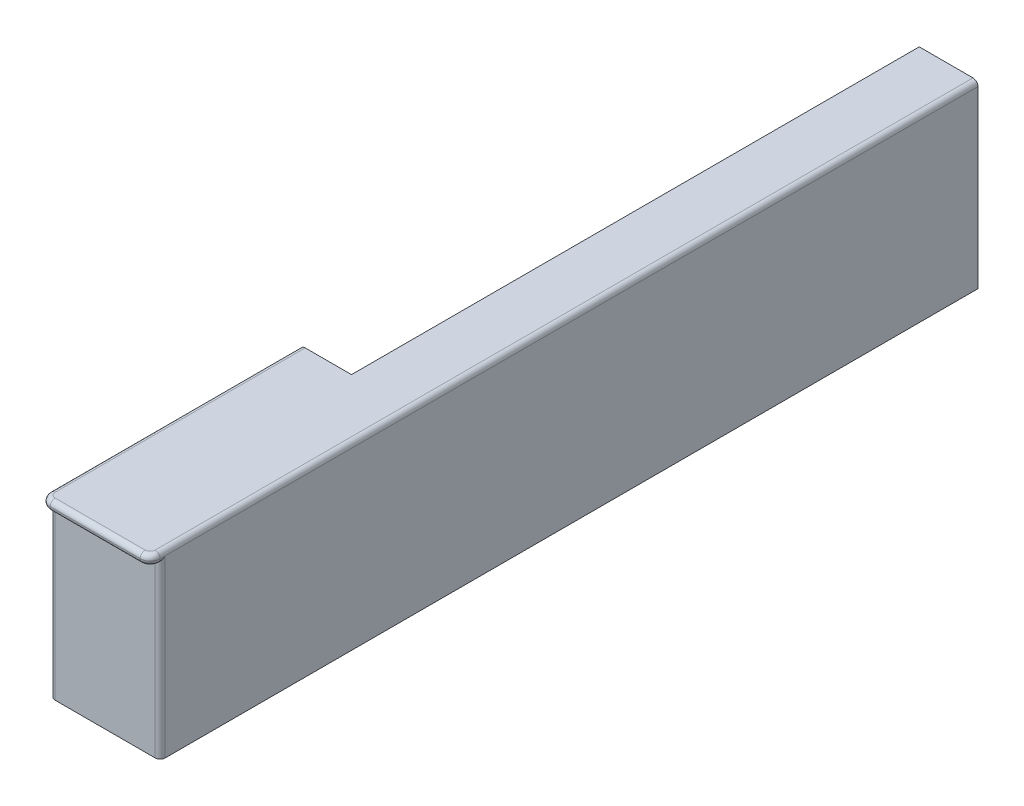
SolidWorks part; units mm, degrees
ref_plane "Front Plane" through (0, 0, 0) normal (0, 0, 1) x (1, 0, 0)
ref_plane "Top Plane" through (0, 0, 0) normal (0, 1, 0) x (1, 0, 0)
ref_plane "Right Plane" through (0, 0, 0) normal (1, 0, 0) x (0, 0, -1)
sketch "Sketch1" plane through (0, 0, 0) normal (0, 1, 0) x (1, 0, 0)
  line L1 (-11, -81.75) -> (11, -81.75)
  line L2 (-11, -81.75) -> (-11, 81.75)
  line L3 (-11, 81.75) -> (11, 81.75)
  line L4 (11, -81.75) -> (11, 81.75)
  line L5 (-11, -81.75) -> (11, 81.75) construction
  line L6 (-11, 81.75) -> (11, -81.75) construction
  point P0 (0, 0)
  dimension "D1" = 163.5
  dimension "D2" = 22
extrude "Boss-Extrude1" add sketch "Sketch1" along normal blind 36 contours L2 L3 L4 L1
fillet "Fillet1" radius 1 2 edges at (-11, 18, 81.75) (11, 18, 81.75)
sketch "Sketch2" plane through (0, 36, 0) normal (0, 1, 0) x (1, 0, 0)
  line L0 (11, -80.75) -> (11, 81.75) construction
  line L1 (-11, 81.75) -> (11, 81.75)
  line L2 (-11, 81.75) -> (-11, -83.75)
  line L3 (-11, -83.75) -> (11, -83.75)
  line L4 (11, 81.75) -> (11, -83.75)
  line L5 (-10, -81.75) -> (10, -81.75) construction
  dimension "D1" = 2
extrude "Boss-Extrude2" add sketch "Sketch2" against normal blind 2
fillet "Fillet2" radius 2 2 edges at (-11, 35, 83.75) (11, 35, 83.75)
fillet "Fillet3" radius 1 10 edges at (-11, 34, 81.25) (-10.4142, 34, 83.1642) (11, 34, 81.25) (10.4142, 34, 83.1642) (11, 36, 0) (10.4142, 36, 83.1642) (0, 36, 83.75) (-10.4142, 36, 83.1642) (-11, 36, 0) (0, 34, 83.75)
sketch "Sketch3" plane through (0, 36, 0) normal (0, 1, 0) x (1, 0, 0)
  line L1 (7.5, -31.75) -> (11, -31.75)
  line L2 (7.5, -31.75) -> (7.5, 81.75)
  line L3 (7.5, 81.75) -> (11, 81.75)
  line L4 (11, -31.75) -> (11, 81.75)
  line L5 (7.5, -31.75) -> (11, 81.75) construction
  line L6 (7.5, 81.75) -> (11, -31.75) construction
  line L7 (-10, -81.75) -> (10, -81.75) construction
  line L8 (-11, 81.75) -> (11, 81.75) construction
  line L9 (11, 81.75) -> (11, -80.75) construction
  dimension "D1" = 3.5
  dimension "D2" = 50
extrude "Cut-Extrude2" [suppressed] cut sketch "Sketch3" against normal through all
sketch "Sketch5" plane through (-11, 0, 0) normal (-1, 0, 0) x (0, 0, 1)
  line L0 (81.75, 34) -> (81.75, 0) construction
  line L1 (80.75, 0) -> (-81.75, 0) construction
  line L2 (-81.75, 36) -> (81.75, 36) construction
  line L3 (-81.75, 35) -> (-81.75, 0) construction
  line L8 (31.75, 36) -> (-81.75, 36)
  line L9 (31.75, 0) -> (31.75, 36)
  line L10 (-81.75, 0) -> (31.75, 0)
  line L11 (-81.75, 36) -> (-81.75, 0)
  dimension "D1" = 50
extrude "Cut-Extrude4" [suppressed] cut sketch "Sketch5" against normal blind 3.5
sketch "Sketch4" [suppressed] plane through (7.5, 0, 0) normal (1, 0, 0) x (0, 0, -1)
  line L4 (81.75, 36) -> (-31.75, 36)
  line L5 (-31.75, 36) -> (-31.75, 0)
  line L6 (-31.75, 0) -> (81.75, 0)
  line L7 (81.75, 0) -> (81.75, 36)
  line L8 (81.75, 36) -> (-31.75, 36)
  line L9 (-31.75, 36) -> (-31.75, 0)
  line L10 (-31.75, 0) -> (81.75, 0)
  line L11 (81.75, 0) -> (81.75, 36)
  dimension "D1" = 0
extrude "Cut-Extrude3" [suppressed] cut sketch "Sketch4" against normal blind 3.25
sketch "Sketch6" [suppressed] plane through (-7.5, 0, 0) normal (-1, 0, 0) x (0, 0, 1)
  line L4 (-81.75, 36) -> (-81.75, 0)
  line L5 (-81.75, 0) -> (31.75, 0)
  line L6 (31.75, 0) -> (31.75, 36)
  line L7 (31.75, 36) -> (-81.75, 36)
  line L8 (-81.75, 36) -> (-81.75, 0)
  line L9 (-81.75, 0) -> (31.75, 0)
  line L10 (31.75, 0) -> (31.75, 36)
  line L11 (31.75, 36) -> (-81.75, 36)
  dimension "D1" = 0
extrude "Cut-Extrude5" [suppressed] cut sketch "Sketch6" against normal blind 3.25
sketch "White" plane through (0, 0, 0) normal (0, 1, 0) x (1, 0, 0)
  line L0 (12.5, -81.75) -> (34.5, -81.75)
  line L1 (-11, -81.75) -> (11, -81.75)
  line L2 (-11, -81.75) -> (-11, 81.75)
  line L3 (-11, 81.75) -> (11, 81.75)
  line L4 (11, -81.75) -> (11, 81.75)
  line L5 (12.5, -81.75) -> (12.5, 81.75)
  line L6 (12.5, 81.75) -> (34.5, 81.75)
  line L7 (34.5, -81.75) -> (34.5, 81.75)
  line L8 (36, -81.75) -> (58, -81.75)
  line L9 (36, -81.75) -> (36, 81.75)
  line L10 (36, 81.75) -> (58, 81.75)
  line L11 (58, -81.75) -> (58, 81.75)
  line L12 (59.5, -81.75) -> (81.5, -81.75)
  line L13 (59.5, -81.75) -> (59.5, 81.75)
  line L14 (59.5, 81.75) -> (81.5, 81.75)
  line L15 (81.5, -81.75) -> (81.5, 81.75)
  line L16 (83, -81.75) -> (105, -81.75)
  line L17 (83, -81.75) -> (83, 81.75)
  line L18 (83, 81.75) -> (105, 81.75)
  line L19 (105, -81.75) -> (105, 81.75)
  line L20 (106.5, -81.75) -> (128.5, -81.75)
  line L21 (106.5, -81.75) -> (106.5, 81.75)
  line L22 (106.5, 81.75) -> (128.5, 81.75)
  line L23 (128.5, -81.75) -> (128.5, 81.75)
  line L24 (130, -81.75) -> (152, -81.75)
  line L25 (130, -81.75) -> (130, 81.75)
  line L26 (130, 81.75) -> (152, 81.75)
  line L27 (152, -81.75) -> (152, 81.75)
  dimension "D1" = 7
sketch "Black" plane through (0, 0, 0) normal (0, 1, 0) x (1, 0, 0)
  line L0 (-11, 81.75) -> (11, 81.75) construction
  line L1 (16, -31.75) -> (4, -31.75)
  line L2 (16, -31.75) -> (16, 81.75)
  line L3 (16, 81.75) -> (4, 81.75)
  line L4 (4, -31.75) -> (4, 81.75)
  line L6 (31, -31.75) -> (43, -31.75)
  line L7 (31, -31.75) -> (31, 81.75)
  line L8 (31, 81.75) -> (43, 81.75)
  line L9 (43, -31.75) -> (43, 81.75)
  line L10 (12.5, -81.75) -> (34.5, -81.75) construction
  line L11 (16, -31.75) -> (31, -31.75) construction
  line L12 (36, 81.75) -> (58, 81.75) construction
  line L13 (106.5, 81.75) -> (128.5, 81.75) construction
  line L14 (111.75, 81.75) -> (99.75, 81.75)
  line L15 (111.75, 81.75) -> (111.75, -31.75)
  line L16 (111.75, -31.75) -> (99.75, -31.75)
  line L17 (99.75, 81.75) -> (99.75, -31.75)
  line L18 (83, 81.75) -> (105, 81.75) construction
  line L19 (126.75, 81.75) -> (138.75, 81.75)
  line L20 (126.75, 81.75) -> (126.75, -31.75)
  line L21 (126.75, -31.75) -> (138.75, -31.75)
  line L22 (138.75, 81.75) -> (138.75, -31.75)
  line L23 (84.75, 81.75) -> (72.75, 81.75)
  line L24 (84.75, 81.75) -> (84.75, -31.75)
  line L25 (84.75, -31.75) -> (72.75, -31.75)
  line L26 (72.75, 81.75) -> (72.75, -31.75)
  line L27 (105, -81.75) -> (106.5, -81.75) construction
  point P14 (23.5, -81.75)
  point P15 (23.5, -31.75)
  point P36 (105.75, -81.75)
  point P37 (105.75, -31.75)
  dimension "D1" = 50
  dimension "D2" = 12
  dimension "D3" = 12
  dimension "D4" = 15
  dimension "D5" = 15
  dimension "D6" = 15
sketch "Sketch11" plane through (0, 36, 0) normal (0, 1, 0) x (1, 0, 0)
  line L1 (11, 81.75) -> (2.5, 81.75)
  line L2 (11, 81.75) -> (11, -31.75)
  line L3 (11, -31.75) -> (2.5, -31.75)
  line L4 (2.5, 81.75) -> (2.5, -31.75)
  line L5 (16, -31.75) -> (4, -31.75) construction
  dimension "D1" = 8.5
extrude "C" [suppressed] cut sketch "Sketch11" against normal through all
sketch "Sketch12" plane through (0, 36, 0) normal (0, 1, 0) x (1, 0, 0)
  line L0 (31, -31.75) -> (43, -31.75) construction
  line L1 (-11, 81.75) -> (-6, 81.75)
  line L2 (-11, 81.75) -> (-11, -31.75)
  line L3 (-11, -31.75) -> (-6, -31.75)
  line L4 (-6, 81.75) -> (-6, -31.75)
  line L5 (11, 81.75) -> (6, 81.75)
  line L6 (11, 81.75) -> (11, -31.75)
  line L7 (11, -31.75) -> (6, -31.75)
  line L8 (6, 81.75) -> (6, -31.75)
  dimension "D1" = 5
  dimension "D2" = 5
extrude "D" [suppressed] cut sketch "Sketch12" against normal through all
sketch "Sketch13" plane through (0, 36, 0) normal (0, 1, 0) x (1, 0, 0)
  line L1 (-11, 81.75) -> (-2.5, 81.75)
  line L2 (-11, 81.75) -> (-11, -31.75)
  line L3 (-11, -31.75) -> (-2.5, -31.75)
  line L4 (-2.5, 81.75) -> (-2.5, -31.75)
  line L5 (16, -31.75) -> (4, -31.75) construction
  dimension "D1" = 8.5
extrude "E" [suppressed] cut sketch "Sketch13" against normal through all
sketch "Sketch14" plane through (0, 36, 0) normal (0, 1, 0) x (1, 0, 0)
  line L0 (16, -31.75) -> (4, -31.75) construction
  line L1 (11, 81.75) -> (0.75, 81.75)
  line L2 (11, 81.75) -> (11, -31.75)
  line L3 (11, -31.75) -> (0.75, -31.75)
  line L4 (0.75, 81.75) -> (0.75, -31.75)
  dimension "D1" = 10.25
extrude "F" [suppressed] cut sketch "Sketch14" against normal through all
sketch "Sketch15" plane through (0, 36, 0) normal (0, 1, 0) x (1, 0, 0)
  line L1 (-11, 81.75) -> (-7.75, 81.75)
  line L2 (-11, 81.75) -> (-11, -31.75)
  line L3 (-11, -31.75) -> (-7.75, -31.75)
  line L4 (-7.75, 81.75) -> (-7.75, -31.75)
  line L5 (11, 81.75) -> (4.25, 81.75)
  line L6 (11, 81.75) -> (11, -31.75)
  line L7 (11, -31.75) -> (4.25, -31.75)
  line L8 (4.25, 81.75) -> (4.25, -31.75)
  line L9 (16, -31.75) -> (4, -31.75) construction
  dimension "D1" = 3.25
  dimension "D2" = 6.75
extrude "G" [suppressed] cut sketch "Sketch15" against normal through all
sketch "Sketch16" plane through (0, 36, 0) normal (0, 1, 0) x (1, 0, 0)
  line L0 (16, -31.75) -> (4, -31.75) construction
  line L1 (-11, 81.75) -> (-4.25, 81.75)
  line L2 (-11, 81.75) -> (-11, -31.75)
  line L3 (-11, -31.75) -> (-4.25, -31.75)
  line L4 (-4.25, 81.75) -> (-4.25, -31.75)
  line L5 (11, 81.75) -> (7.75, 81.75)
  line L6 (11, 81.75) -> (11, -31.75)
  line L7 (11, -31.75) -> (7.75, -31.75)
  line L8 (7.75, 81.75) -> (7.75, -31.75)
  dimension "D1" = 6.75
  dimension "D2" = 3.25
extrude "A" [suppressed] cut sketch "Sketch16" against normal through all
sketch "Sketch17" plane through (0, 36, 0) normal (0, 1, 0) x (1, 0, 0)
  line L0 (16, -31.75) -> (4, -31.75) construction
  line L1 (-11, 81.75) -> (-0.75, 81.75)
  line L2 (-11, 81.75) -> (-11, -31.75)
  line L3 (-11, -31.75) -> (-0.75, -31.75)
  line L4 (-0.75, 81.75) -> (-0.75, -31.75)
  dimension "D1" = 10.25
extrude "B" cut sketch "Sketch17" against normal through all
